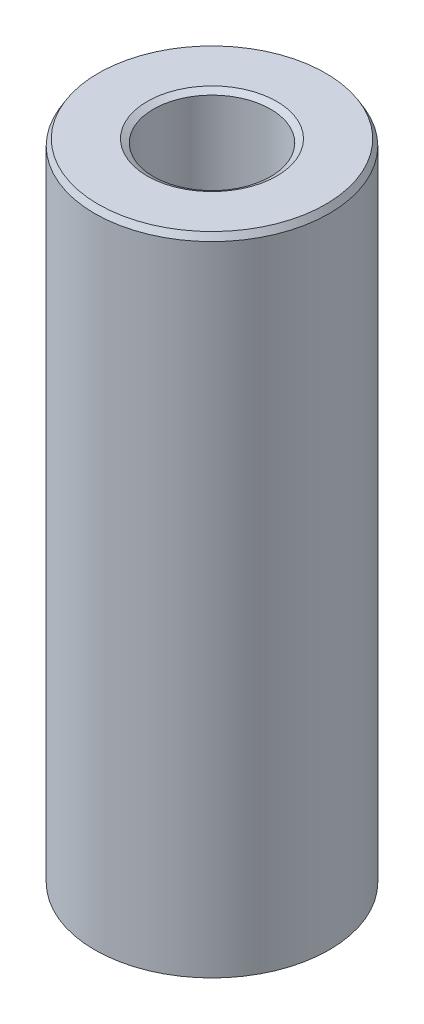
SolidWorks part; units mm, degrees
ref_plane "Front Plane" through (0, 0, 0) normal (0, 0, 1) x (1, 0, 0)
ref_plane "Top Plane" through (0, 0, 0) normal (0, 1, 0) x (1, 0, 0)
ref_plane "Right Plane" through (0, 0, 0) normal (1, 0, 0) x (0, 0, -1)
sketch "Sketch1" plane through (0, 0, 0) normal (0, 1, 0) x (1, 0, 0)
  circle A0 centre (0, 0) radius 22.5
  dimension "SLEEVE_OD" = 45
extrude "Boss-Extrude1" add sketch "Sketch1" along normal blind 124.2592
sketch "Sketch2" plane through (0, 0, 0) normal (0, 1, 0) x (1, 0, 0)
  circle A0 centre (0, 0) radius 11.2343
  dimension "BORE_D" = 22.4687
extrude "Cut-Extrude1" cut sketch "Sketch2" along normal through all
chamfer "Chamfer1" distance 1.1875 angle 30 4 edges at (0, 124.2592, 11.2343) (0, 0, 11.2343) (0, 0, 22.5) (0, 124.2592, 22.5) first distance on face at (0, 124.2592, 11.2343) first distance on face at (0, 0, 11.2343) first distance on face at (0, 124.2592, 22.5)
